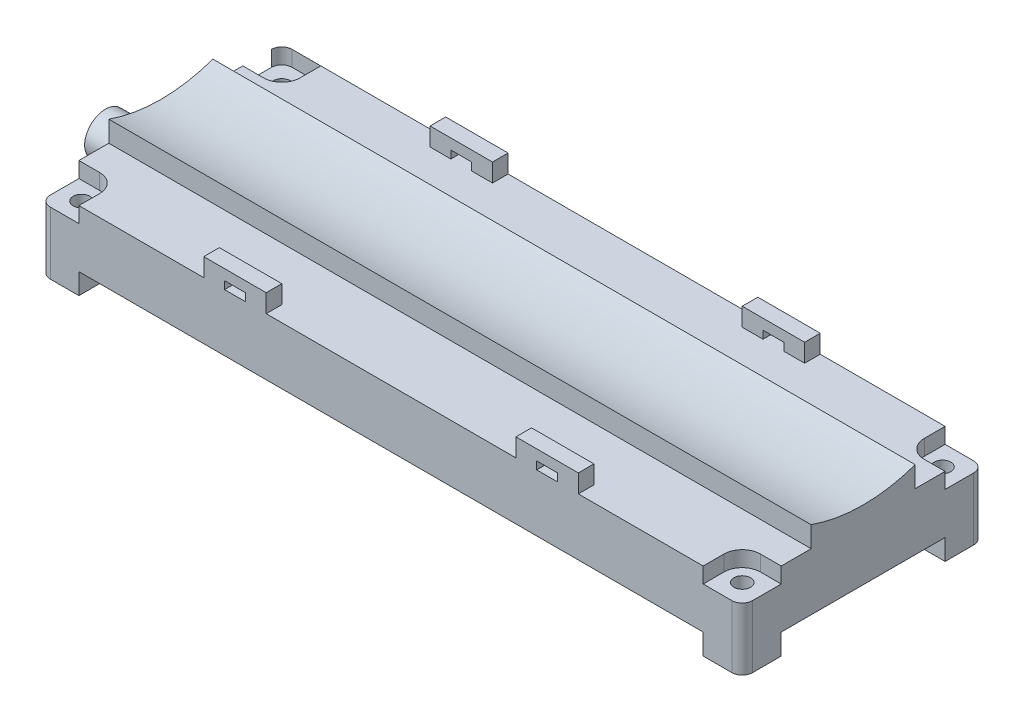
SolidWorks part; units mm, degrees
material "PA Type 6"
ref_plane "Front Plane" through (0, 0, 0) normal (0, 0, 1) x (1, 0, 0)
ref_plane "Top Plane" through (0, 0, 0) normal (0, 1, 0) x (1, 0, 0)
ref_plane "Right Plane" through (0, 0, 0) normal (1, 0, 0) x (0, 0, -1)
sketch "Sketch1" plane through (0, 0, 0) normal (0, 1, 0) x (1, 0, 0)
  line L0 (63.5, 19.25) -> (-63.5, 19.25) construction
  line L1 (65.5, -23.25) -> (-65.5, -23.25)
  line L2 (67.5, -21.25) -> (67.5, 21.25)
  line L3 (65.5, 23.25) -> (-65.5, 23.25)
  line L4 (-67.5, -21.25) -> (-67.5, 21.25)
  line L5 (67.5, -23.25) -> (-67.5, 23.25) construction
  line L6 (67.5, 23.25) -> (-67.5, -23.25) construction
  line L11 (-4.5, 3.75) -> (42.5, -19.25) construction
  line L12 (-4.5, -19.25) -> (42.5, 3.75) construction
  line L13 (-67.5, 0) -> (67.5, 0) construction
  line L14 (-63.5, -19.25) -> (-63.5, 19.25) construction
  line L15 (63.5, -19.25) -> (-63.5, -19.25) construction
  line L16 (63.5, -19.25) -> (63.5, 19.25) construction
  line L17 (-4.5, -19.25) -> (-4.5, 3.75) construction
  line L18 (-4.5, 3.75) -> (42.5, 3.75) construction
  line L19 (42.5, -19.25) -> (42.5, 3.75) construction
  line L20 (-4.5, -19.25) -> (42.5, -19.25) construction
  line L21 (67.5, -23.25) -> (67.5, 23.25) construction
  line L22 (67.5, -23.25) -> (-67.5, -23.25) construction
  line L23 (67.5, 23.25) -> (-67.5, 23.25) construction
  line L24 (-67.5, -23.25) -> (-67.5, 23.25) construction
  line L25 (-59.5, 0) -> (-24.5, 0) construction
  line L27 (42.5, 3.75) -> (42.5, -19.25) construction
  line L28 (-59.5, -12.4) -> (-11.5, -12.4) construction
  line L29 (34.42, -20.42) -> (57.5, -20.42) construction
  line L30 (34.42, -20.42) -> (34.42, 20.42) construction
  line L31 (34.42, 20.42) -> (57.5, 20.42) construction
  line L38 (57.5, -20.42) -> (57.5, 20.42) construction
  line L39 (34.42, -20.42) -> (57.5, 20.42) construction
  line L40 (34.42, 20.42) -> (57.5, -20.42) construction
  line L41 (-59.5, -12.4) -> (-59.5, -2.4) construction
  line L42 (-59.5, -2.4) -> (-11.5, -2.4) construction
  line L43 (-11.5, -12.4) -> (-11.5, -2.4) construction
  line L44 (-59.5, -12.4) -> (-11.5, -2.4) construction
  line L45 (-59.5, -2.4) -> (-11.5, -12.4) construction
  line L46 (-55, -17.4) -> (-16, -17.4) construction
  line L47 (-55.5, -16.9) -> (-55.5, 2.1) construction
  line L48 (-55, 2.6) -> (-16, 2.6) construction
  line L49 (-15.5, -16.9) -> (-15.5, 2.1) construction
  line L50 (-55.5, -17.4) -> (-15.5, 2.6) construction
  line L51 (-55.5, 2.6) -> (-15.5, -17.4) construction
  circle A6 centre (-63.5, 19.25) radius 2.25 construction
  circle A7 centre (-63.5, -19.25) radius 2.25 construction
  circle A8 centre (63.5, -19.25) radius 2.25 construction
  circle A9 centre (63.5, 19.25) radius 2.25 construction
  arc A16 (67.5, -21.25) -> (65.5, -23.25) centre (65.5, -21.25) cw
  arc A17 (65.5, 23.25) -> (67.5, 21.25) centre (65.5, 21.25) cw
  arc A18 (-65.5, 23.25) -> (-67.5, 21.25) centre (-65.5, 21.25) ccw
  arc A19 (-65.5, -23.25) -> (-67.5, -21.25) centre (-65.5, -21.25) cw
  arc A33 (-55.5, -16.9) -> (-55, -17.4) centre (-55, -16.9) ccw construction
  arc A34 (-16, -17.4) -> (-15.5, -16.9) centre (-16, -16.9) ccw construction
  arc A35 (-15.5, 2.1) -> (-16, 2.6) centre (-16, 2.1) ccw construction
  arc A36 (-55, 2.6) -> (-55.5, 2.1) centre (-55, 2.1) ccw construction
  circle A37 centre (-45.5, -7.4) radius 12.05 construction
  circle A38 centre (-59.5, -2.4) radius 2 construction
  circle A39 centre (-59.5, -12.4) radius 2 construction
  circle A40 centre (-11.5, -2.4) radius 2 construction
  circle A41 centre (-11.5, -12.4) radius 2 construction
  point P0 (0, 0)
  point P6 (45.96, 0)
  point P16 (-35.5, -7.4)
  point P51 (-35.5, -7.4)
  point P85 (-45.5, -7.4)
  point P92 (-45.5, 4.65)
  dimension "D6" = 4.5
  dimension "D7" = 4
  dimension "D8" = 23.08
  dimension "D9" = 40.84
  dimension "D16" = 2
  dimension "D17" = 20
  dimension "D19" = 0.5
  dimension "D20" = 10
  dimension "D22" = 4
  dimension "D23" = 4
  dimension "D26" = 47
  dimension "D11" = 10
  dimension "D21" = 24.1
  dimension "D1" = 46.5
  dimension "D2" = 135
  dimension "D4" = 48
  dimension "D5" = 35
  dimension "D10" = 10
  dimension "D12" = 8
  dimension "D14" = 25
  dimension "D18" = 40
  dimension "D13" = 23
  dimension "D27" = 2.4
  dimension "D28" = 4.65
extrude "Boss-Extrude1" add sketch "Sketch1" along normal blind 11
shell "Shell1" thickness 1 removed face at (0, 0, 0)
sketch "Sketch4" plane through (0, 10, 0) normal (0, -1, 0) x (1, 0, 0)
  line L0 (63.5, 19.25) -> (-63.5, 19.25) construction
  line L1 (65.5, -23.25) -> (60, -23.25)
  line L2 (67.5, -21.25) -> (67.5, -15.75)
  line L3 (65.5, 23.25) -> (60, 23.25)
  line L4 (-67.5, -21.25) -> (-67.5, -15.75)
  line L5 (67.5, -23.25) -> (-67.5, 23.25) construction
  line L6 (67.5, 23.25) -> (-67.5, -23.25) construction
  line L11 (-4.5, 3.75) -> (42.5, -19.25) construction
  line L12 (-4.5, -19.25) -> (42.5, 3.75) construction
  line L13 (-67.5, 0) -> (67.5, 0) construction
  line L14 (-63.5, -19.25) -> (-63.5, 19.25) construction
  line L15 (63.5, -19.25) -> (-63.5, -19.25) construction
  line L16 (63.5, -19.25) -> (63.5, 19.25) construction
  line L17 (-4.5, -19.25) -> (-4.5, 3.75) construction
  line L18 (-4.5, 3.75) -> (42.5, 3.75) construction
  line L19 (42.5, -19.25) -> (42.5, 3.75) construction
  line L20 (-4.5, -19.25) -> (42.5, -19.25) construction
  line L21 (67.5, -23.25) -> (67.5, 23.25) construction
  line L22 (67.5, -23.25) -> (-67.5, -23.25) construction
  line L23 (67.5, 23.25) -> (-67.5, 23.25) construction
  line L24 (-67.5, -23.25) -> (-67.5, 23.25) construction
  line L25 (-59.5, 0) -> (-24.5, 0) construction
  line L26 (-60, 19.25) -> (-60, 23.25)
  line L27 (42.5, 3.75) -> (42.5, -19.25) construction
  line L28 (-59.5, -12.4) -> (-11.5, -12.4) construction
  line L29 (34.42, -20.42) -> (57.5, -20.42) construction
  line L30 (34.42, -20.42) -> (34.42, 20.42) construction
  line L31 (34.42, 20.42) -> (57.5, 20.42) construction
  line L36 (-63.5, 15.75) -> (-67.5, 15.75)
  line L37 (-63.5, -15.75) -> (-67.5, -15.75)
  line L38 (57.5, -20.42) -> (57.5, 20.42) construction
  line L39 (34.42, -20.42) -> (57.5, 20.42) construction
  line L40 (34.42, 20.42) -> (57.5, -20.42) construction
  line L41 (-59.5, -12.4) -> (-59.5, -2.4) construction
  line L42 (-59.5, -2.4) -> (-11.5, -2.4) construction
  line L43 (-11.5, -12.4) -> (-11.5, -2.4) construction
  line L44 (-59.5, -12.4) -> (-11.5, -2.4) construction
  line L45 (-59.5, -2.4) -> (-11.5, -12.4) construction
  line L46 (-55, -17.4) -> (-16, -17.4) construction
  line L47 (-55.5, -16.9) -> (-55.5, 2.1) construction
  line L48 (-55, 2.6) -> (-16, 2.6) construction
  line L49 (-15.5, -16.9) -> (-15.5, 2.1) construction
  line L50 (-55.5, -17.4) -> (-15.5, 2.6) construction
  line L51 (-55.5, 2.6) -> (-15.5, -17.4) construction
  line L53 (-60, -19.25) -> (-60, -23.25)
  line L55 (-67.5, 15.75) -> (-67.5, 21.25)
  line L56 (60, 19.25) -> (60, 23.25)
  line L57 (63.5, 15.75) -> (67.5, 15.75)
  line L58 (-60, 23.25) -> (-65.5, 23.25)
  line L59 (60, -19.25) -> (60, -23.25)
  line L60 (63.5, -15.75) -> (67.5, -15.75)
  line L61 (67.5, 15.75) -> (67.5, 21.25)
  line L62 (-60, -23.25) -> (-65.5, -23.25)
  arc A6 (-63.5, 15.75) -> (-60, 19.25) centre (-63.5, 19.25) ccw
  arc A7 (-60, -19.25) -> (-63.5, -15.75) centre (-63.5, -19.25) ccw
  arc A8 (63.5, -15.75) -> (60, -19.25) centre (63.5, -19.25) ccw
  arc A9 (60, 19.25) -> (63.5, 15.75) centre (63.5, 19.25) ccw
  arc A16 (67.5, -21.25) -> (65.5, -23.25) centre (65.5, -21.25) cw
  arc A17 (65.5, 23.25) -> (67.5, 21.25) centre (65.5, 21.25) cw
  arc A18 (-65.5, 23.25) -> (-67.5, 21.25) centre (-65.5, 21.25) ccw
  arc A19 (-65.5, -23.25) -> (-67.5, -21.25) centre (-65.5, -21.25) cw
  arc A33 (-55.5, -16.9) -> (-55, -17.4) centre (-55, -16.9) ccw construction
  arc A34 (-16, -17.4) -> (-15.5, -16.9) centre (-16, -16.9) ccw construction
  arc A35 (-15.5, 2.1) -> (-16, 2.6) centre (-16, 2.1) ccw construction
  arc A36 (-55, 2.6) -> (-55.5, 2.1) centre (-55, 2.1) ccw construction
  circle A37 centre (-45.5, -7.4) radius 12.05 construction
  circle A38 centre (-59.5, -2.4) radius 2 construction
  circle A39 centre (-59.5, -12.4) radius 2 construction
  circle A40 centre (-11.5, -2.4) radius 2 construction
  circle A41 centre (-11.5, -12.4) radius 2 construction
  point P0 (0, 0)
  point P6 (45.96, 0)
  point P16 (-35.5, -7.4)
  point P51 (-35.5, -7.4)
  point P85 (-45.5, -7.4)
  point P92 (-45.5, 4.65)
  dimension "D6" = 7
  dimension "D7" = 4
  dimension "D8" = 23.08
  dimension "D9" = 40.84
  dimension "D16" = 2
  dimension "D17" = 20
  dimension "D19" = 0.5
  dimension "D20" = 10
  dimension "D22" = 4
  dimension "D23" = 4
  dimension "D26" = 47
  dimension "D11" = 10
  dimension "D21" = 24.1
  dimension "D1" = 46.5
  dimension "D2" = 135
  dimension "D4" = 48
  dimension "D5" = 35
  dimension "D10" = 10
  dimension "D12" = 8
  dimension "D14" = 25
  dimension "D18" = 40
  dimension "D13" = 23
  dimension "D27" = 2.4
  dimension "D28" = 4.65
extrude "Boss-Extrude2" add sketch "Sketch4" along normal blind 14
sketch "Sketch7" plane through (0, 10, 0) normal (0, -1, 0) x (1, 0, 0)
  line L0 (63.5, 19.25) -> (-63.5, 19.25) construction
  line L1 (65.5, -23.25) -> (60, -23.25)
  line L2 (67.5, -21.25) -> (67.5, -15.75)
  line L3 (65.5, 23.25) -> (60, 23.25)
  line L4 (-67.5, -21.25) -> (-67.5, -15.75)
  line L5 (67.5, -23.25) -> (-67.5, 23.25) construction
  line L6 (67.5, 23.25) -> (-67.5, -23.25) construction
  line L11 (-4.5, 3.75) -> (42.5, -19.25) construction
  line L12 (-4.5, -19.25) -> (42.5, 3.75) construction
  line L14 (-63.5, -19.25) -> (-63.5, 19.25) construction
  line L15 (63.5, -19.25) -> (-63.5, -19.25) construction
  line L16 (63.5, -19.25) -> (63.5, 19.25) construction
  line L17 (-4.5, -19.25) -> (-4.5, 3.75) construction
  line L18 (-4.5, 3.75) -> (42.5, 3.75) construction
  line L19 (42.5, -19.25) -> (42.5, 3.75) construction
  line L20 (-4.5, -19.25) -> (42.5, -19.25) construction
  line L21 (67.5, -23.25) -> (67.5, 23.25) construction
  line L22 (67.5, -23.25) -> (-67.5, -23.25) construction
  line L23 (67.5, 23.25) -> (-67.5, 23.25) construction
  line L24 (-67.5, -23.25) -> (-67.5, 23.25) construction
  line L25 (-59.5, 0) -> (-24.5, 0) construction
  line L27 (42.5, 3.75) -> (42.5, -19.25) construction
  line L28 (-59.5, -12.4) -> (-11.5, -12.4) construction
  line L41 (-59.5, -12.4) -> (-59.5, -2.4) construction
  line L42 (-59.5, -2.4) -> (-11.5, -2.4) construction
  line L43 (-11.5, -12.4) -> (-11.5, -2.4) construction
  line L44 (-59.5, -12.4) -> (-11.5, -2.4) construction
  line L45 (-59.5, -2.4) -> (-11.5, -12.4) construction
  line L46 (-55, -17.4) -> (-16, -17.4) construction
  line L47 (-55.5, -16.9) -> (-55.5, 2.1) construction
  line L48 (-55, 2.6) -> (-16, 2.6) construction
  line L49 (-15.5, -16.9) -> (-15.5, 2.1) construction
  line L50 (-55.5, -17.4) -> (-15.5, 2.6) construction
  line L51 (-55.5, 2.6) -> (-15.5, -17.4) construction
  line L55 (-67.5, 15.75) -> (-67.5, 21.25)
  line L58 (-60, 23.25) -> (-65.5, 23.25)
  line L61 (67.5, 15.75) -> (67.5, 21.25)
  line L62 (-60, -23.25) -> (-65.5, -23.25)
  line L67 (57, -19.25) -> (57, -19.6333)
  line L76 (63.5, 12.75) -> (70.5, 12.75) construction
  line L77 (70.5, 12.75) -> (70.5, 21.25) construction
  line L78 (65.5, 26.25) -> (57, 26.25) construction
  line L79 (57, 19.25) -> (57, 26.25) construction
  line L80 (57, -19.25) -> (57, -26.25) construction
  line L81 (65.5, -26.25) -> (57, -26.25) construction
  line L82 (70.5, -21.25) -> (70.5, -12.75) construction
  line L83 (63.5, -12.75) -> (70.5, -12.75) construction
  line L84 (-57, -19.25) -> (-57, -26.25) construction
  line L85 (-57, -26.25) -> (-65.5, -26.25) construction
  line L86 (-70.5, -21.25) -> (-70.5, -12.75) construction
  line L87 (-63.5, -12.75) -> (-70.5, -12.75) construction
  line L88 (-63.5, 12.75) -> (-70.5, 12.75) construction
  line L89 (-70.5, 12.75) -> (-70.5, 21.25) construction
  line L90 (-57, 26.25) -> (-65.5, 26.25) construction
  line L91 (-57, 19.25) -> (-57, 26.25) construction
  line L92 (63.5, 15.75) -> (67.5, 15.75) construction
  line L93 (60, 19.25) -> (60, 23.25) construction
  line L94 (57, 19.25) -> (57, 23.25)
  line L96 (57, 23.25) -> (60, 23.25)
  line L97 (63.5, 12.75) -> (67.5, 12.75)
  line L99 (67.5, 12.75) -> (67.5, 15.75)
  line L100 (63.5, -12.75) -> (67.5, -12.75)
  line L101 (57, -19.6333) -> (57, -23.25)
  line L102 (57, -23.25) -> (60, -23.25)
  line L103 (60, -19.25) -> (60, -23.25) construction
  line L104 (63.5, -15.75) -> (67.5, -15.75) construction
  line L105 (67.5, -12.75) -> (67.5, -15.75)
  line L106 (-57, -19.25) -> (-57, -23.25)
  line L107 (-57, -23.25) -> (-60, -23.25)
  line L108 (-63.5, -12.75) -> (-67.5, -12.75)
  line L109 (-67.5, -12.75) -> (-67.5, -15.75)
  line L110 (-60, -19.25) -> (-60, -23.25) construction
  line L111 (-63.5, -15.75) -> (-67.5, -15.75) construction
  line L112 (-57, 19.25) -> (-57, 23.25)
  line L113 (-57, 23.25) -> (-60, 23.25)
  line L114 (-63.5, 12.75) -> (-67.5, 12.75)
  line L115 (-67.5, 12.75) -> (-67.5, 15.75)
  line L116 (-60, 19.25) -> (-60, 23.25) construction
  line L117 (-63.5, 15.75) -> (-67.5, 15.75) construction
  arc A16 (67.5, -21.25) -> (65.5, -23.25) centre (65.5, -21.25) cw
  arc A17 (65.5, 23.25) -> (67.5, 21.25) centre (65.5, 21.25) cw
  arc A18 (-65.5, 23.25) -> (-67.5, 21.25) centre (-65.5, 21.25) ccw
  arc A19 (-65.5, -23.25) -> (-67.5, -21.25) centre (-65.5, -21.25) cw
  arc A33 (-55.5, -16.9) -> (-55, -17.4) centre (-55, -16.9) ccw construction
  arc A34 (-16, -17.4) -> (-15.5, -16.9) centre (-16, -16.9) ccw construction
  arc A35 (-15.5, 2.1) -> (-16, 2.6) centre (-16, 2.1) ccw construction
  arc A36 (-55, 2.6) -> (-55.5, 2.1) centre (-55, 2.1) ccw construction
  circle A37 centre (-45.5, -7.4) radius 12.05 construction
  circle A38 centre (-59.5, -2.4) radius 2 construction
  circle A39 centre (-59.5, -12.4) radius 2 construction
  circle A40 centre (-11.5, -2.4) radius 2 construction
  circle A41 centre (-11.5, -12.4) radius 2 construction
  arc A43 (57, 19.25) -> (63.5, 12.75) centre (63.5, 19.25) ccw
  arc A45 (63.5, -12.75) -> (57, -19.25) centre (63.5, -19.25) ccw
  arc A46 (-63.5, 12.75) -> (-57, 19.25) centre (-63.5, 19.25) ccw
  arc A49 (-57, -19.25) -> (-63.5, -12.75) centre (-63.5, -19.25) ccw
  arc A50 (65.5, 26.25) -> (70.5, 21.25) centre (65.5, 21.25) cw construction
  arc A51 (70.5, -21.25) -> (65.5, -26.25) centre (65.5, -21.25) cw construction
  arc A52 (-65.5, -26.25) -> (-70.5, -21.25) centre (-65.5, -21.25) cw construction
  arc A53 (-65.5, 26.25) -> (-70.5, 21.25) centre (-65.5, 21.25) ccw construction
  arc A54 (60, 19.25) -> (63.5, 15.75) centre (63.5, 19.25) ccw construction
  arc A55 (63.5, -15.75) -> (60, -19.25) centre (63.5, -19.25) ccw construction
  arc A56 (-60, -19.25) -> (-63.5, -15.75) centre (-63.5, -19.25) ccw construction
  arc A57 (-63.5, 15.75) -> (-60, 19.25) centre (-63.5, 19.25) ccw construction
  point P0 (0, 0)
  point P16 (-35.5, -7.4)
  point P51 (-35.5, -7.4)
  point P85 (-45.5, -7.4)
  point P92 (-45.5, 4.65)
  dimension "D7" = 4
  dimension "D16" = 2
  dimension "D17" = 20
  dimension "D19" = 0.5
  dimension "D20" = 10
  dimension "D22" = 4
  dimension "D23" = 4
  dimension "D26" = 47
  dimension "D11" = 10
  dimension "D21" = 24.1
  dimension "D1" = 46.5
  dimension "D2" = 135
  dimension "D3" = 3
  dimension "D4" = 48
  dimension "D5" = 35
  dimension "D12" = 8
  dimension "D14" = 25
  dimension "D18" = 40
  dimension "D13" = 23
extrude "Boss-Extrude3" add sketch "Sketch7" along normal blind 4
sketch "Sketch5" plane through (0, 11, 0) normal (0, 1, 0) x (1, 0, 0)
  line L1 (63.5, -19.25) -> (-63.5, -19.25) construction
  line L2 (63.5, -19.25) -> (63.5, 19.25) construction
  line L3 (63.5, 19.25) -> (-63.5, 19.25) construction
  line L4 (-63.5, -19.25) -> (-63.5, 19.25) construction
  line L5 (63.5, -19.25) -> (-63.5, 19.25) construction
  line L6 (63.5, 19.25) -> (-63.5, -19.25) construction
  circle A0 centre (-63.5, 19.25) radius 1.6
  circle A1 centre (-63.5, -19.25) radius 1.6
  circle A2 centre (63.5, 19.25) radius 1.6
  circle A3 centre (63.5, -19.25) radius 1.6
  point P0 (0, 0)
  dimension "D1" = 3.2
  dimension "D2" = 127
  dimension "D3" = 38.5
extrude "Cut-Extrude1" cut sketch "Sketch5" against normal through all both and the other way through all
sketch "Sketch12" plane through (0, 11, 0) normal (0, 1, 0) x (1, 0, 0)
  line L0 (-63.5, 15.75) -> (-67.5, 15.75)
  line L1 (-63.5, -19.25) -> (63.5, -19.25) construction
  line L2 (-63.5, -19.25) -> (-63.5, 19.25) construction
  line L3 (-63.5, 19.25) -> (63.5, 19.25) construction
  line L4 (63.5, -19.25) -> (63.5, 19.25) construction
  line L5 (-63.5, -19.25) -> (63.5, 19.25) construction
  line L6 (-63.5, 19.25) -> (63.5, -19.25) construction
  line L7 (-67.5, 15.75) -> (-67.5, 21.25)
  line L8 (-60, 19.25) -> (-60, 23.2481)
  line L9 (-60, 23.2481) -> (-65.5019, 23.2481)
  line L10 (-63.5, -15.75) -> (-67.5, -15.75)
  line L11 (-67.5, -15.75) -> (-67.5, -21.25)
  line L12 (-60, -19.25) -> (-60, -23.25)
  line L13 (-60, -23.25) -> (-65.5, -23.25)
  line L14 (60, -19.25) -> (60, -23.25)
  line L15 (60, -23.25) -> (65.5, -23.25)
  line L16 (63.5, -15.75) -> (67.5, -15.75)
  line L17 (67.5, -15.75) -> (67.5, -21.25)
  line L18 (60, 19.25) -> (60, 23.25)
  line L19 (60, 23.25) -> (65.5, 23.25)
  line L20 (63.5, 15.75) -> (67.5, 15.75)
  line L21 (67.5, 15.75) -> (67.5, 21.25)
  arc A0 (-63.5, 15.75) -> (-60, 19.25) centre (-63.5, 19.25) ccw
  arc A1 (-60, -19.25) -> (-63.5, -15.75) centre (-63.5, -19.25) ccw
  arc A2 (60, 19.25) -> (63.5, 15.75) centre (63.5, 19.25) ccw
  arc A3 (63.5, -15.75) -> (60, -19.25) centre (63.5, -19.25) ccw
  arc A4 (-67.5, 21.25) -> (-65.5019, 23.2481) centre (-65.5019, 21.25) cw
  arc A5 (-65.5, -23.25) -> (-67.5, -21.25) centre (-65.5, -21.25) cw
  arc A6 (67.5, -21.25) -> (65.5, -23.25) centre (65.5, -21.25) cw
  arc A7 (65.5, 23.25) -> (67.5, 21.25) centre (65.5, 21.25) cw
  point P0 (0, 0)
  dimension "D1" = 7
extrude "Cut-Extrude3" cut sketch "Sketch12" against normal blind 3
sketch "Sketch13" plane through (0, 10, 0) normal (0, -1, 0) x (1, 0, 0)
  circle A0 centre (-45.5, -7.4) radius 2.75
  dimension "D1" = 5.5
extrude "Boss-Extrude4" add sketch "Sketch13" along normal blind 2
sketch "Sketch14" plane through (-67.5, 0, 0) normal (-1, 0, 0) x (0, 0, 1)
  line L0 (-15.75, 11) -> (15.75, 11) construction
  line L1 (0, 0) -> (0, 11) construction
  line L2 (-15.75, 0) -> (15.75, 0) construction
  circle A1 centre (4.65, 7) radius 4
  dimension "D1" = 8
  dimension "D2" = 4
  dimension "D3" = 4.65
extrude "Boss-Extrude5" add sketch "Sketch14" along normal blind 6
sketch "Sketch15" plane through (67.5, 0, 0) normal (1, 0, 0) x (0, 0, -1)
  line L0 (-15.75, 11) -> (15.75, 11) construction
  line L1 (-10, 15) -> (10, 15) construction
  line L2 (-10, 15) -> (-10, 11)
  line L3 (-10, 11) -> (10, 11)
  line L4 (10, 15) -> (10, 11)
  line L5 (-10, 15) -> (10, 11) construction
  line L6 (-10, 11) -> (10, 15) construction
  line L7 (0, 13) -> (0, 0) construction
  line L8 (-15.75, 0) -> (15.75, 0) construction
  line L9 (0, 13) -> (0, 43.2843) construction
  arc A0 (-10, 15) -> (10, 15) centre (0, 43.2843) ccw
  point P0 (0, 13)
  dimension "D3" = 60
  dimension "D1" = 4
  dimension "D2" = 20
extrude "Boss-Extrude6" add sketch "Sketch15" against normal up to vertex (135 mm away) up to point (-67.5, 11, 4.65)
sketch "Sketch16" plane through (0, 0, 23.25) normal (0, 0, 1) x (1, 0, 0)
  line L0 (0, -4.584) -> (0, 31.5355) construction
  line L1 (-36, 11) -> (-32, 11)
  line L2 (-36, 11) -> (-36, 14.5)
  line L3 (-36, 14.5) -> (-24, 14.5)
  line L4 (-24, 11) -> (-24, 14.5)
  line L5 (-36, 11) -> (-24, 14.5) construction
  line L6 (-36, 14.5) -> (-24, 11) construction
  line L7 (-60, 0) -> (60, 0) construction
  line L8 (-28, 11) -> (-24, 11)
  line L9 (24, 11) -> (28, 11)
  line L10 (24, 11) -> (24, 14.5)
  line L11 (24, 14.5) -> (36, 14.5)
  line L12 (36, 11) -> (36, 14.5)
  line L13 (24, 11) -> (36, 14.5) construction
  line L14 (24, 14.5) -> (36, 11) construction
  line L20 (-32, 12.5) -> (-28, 12.5)
  line L21 (-32, 12.5) -> (-32, 11)
  line L23 (-28, 12.5) -> (-28, 11)
  line L24 (-32, 12.5) -> (-28, 11) construction
  line L25 (-32, 11) -> (-28, 12.5) construction
  line L26 (32, 11) -> (32, 12.5)
  line L27 (32, 12.5) -> (28, 12.5)
  line L28 (28, 11) -> (28, 12.5)
  line L29 (32, 11) -> (28, 12.5) construction
  line L30 (32, 12.5) -> (28, 11) construction
  line L31 (-30, 12.75) -> (-30, 11) construction
  line L32 (30, 12.75) -> (30, 11) construction
  line L33 (-60, 11) -> (60, 11) construction
  line L34 (32, 11) -> (36, 11)
  point P0 (-30, 12.75)
  point P7 (30, 12.75)
  point P14 (-30, 11.75)
  point P17 (0, 0)
  point P26 (30, 11.75)
  dimension "D1" = 30
  dimension "D2" = 30
  dimension "D3" = 12
  dimension "D4" = 12
  dimension "D5" = 3.5
  dimension "D6" = 3.5
  dimension "D7" = 1.5
  dimension "D8" = 4
extrude "Boss-Extrude7" add sketch "Sketch16" against normal blind 3
mirror "Mirror1" about plane through (0, 0, 0) normal (0, 0, 1) of "Boss-Extrude7"
